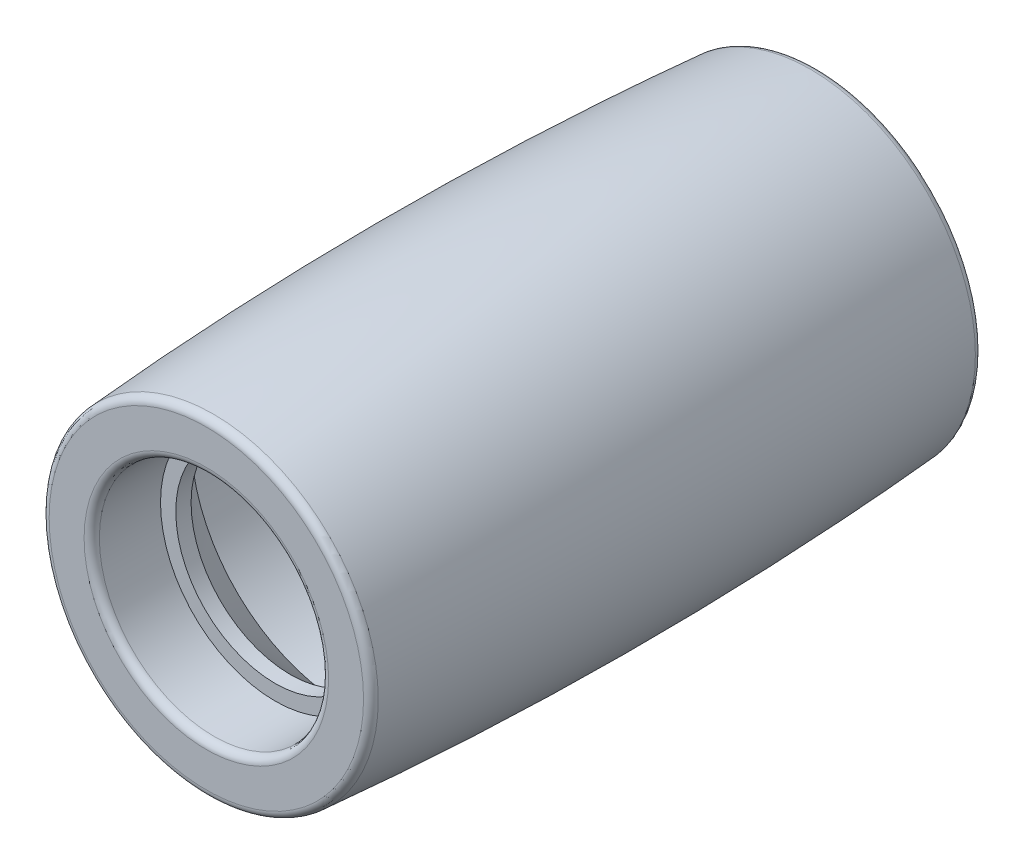
SolidWorks part; units mm, degrees
ref_plane "Ebene vorne" through (0, 0, 0) normal (0, 0, 1) x (1, 0, 0)
ref_plane "Ebene oben" through (0, 0, 0) normal (0, 1, 0) x (1, 0, 0)
ref_plane "Ebene rechts" through (0, 0, 0) normal (1, 0, 0) x (0, 0, -1)
sketch "Skizze1" plane through (450, 0, 0) normal (1, 0, 0) x (0, 0, -1)
  line L7 (20.5, 20.2121) -> (49.5, 20.2121) construction
  line L16 (49.5, 23) -> (49.5, 20.2121) construction
  line L17 (9.5, 21.5) -> (9.5, 15) construction
  line L18 (18.5, 15) -> (9.5, 15) construction
  line L19 (18.5, 15) -> (18.5, 5) construction
  line L20 (18.5, 13) -> (20.5, 13) construction
  line L21 (20.5, 13) -> (27.7121, 20.2121) construction
  line L22 (0, 0) -> (99, 0) construction
  line L23 (27.7121, 20.2121) -> (49.5, 20.2121)
  line L24 (49.5, 23) -> (49.5, 20.2121)
  line L25 (9.5, 21.5) -> (9.5, 15)
  line L26 (18.5, 15) -> (9.5, 15)
  line L27 (18.5, 15) -> (18.5, 13)
  line L28 (18.5, 13) -> (20.5, 13)
  line L29 (20.5, 13) -> (27.7121, 20.2121)
  line L30 (0, 0) -> (99, 0) construction
  arc A2 (89.5, 21.5) -> (9.5, 21.5) centre (49.5, -511.0833) ccw construction
  arc A3 (49.5, 23) -> (9.5, 21.5) centre (49.5, -511.0833) ccw
revolve "Rotation1" add sketch "Skizze1" angle 360 about L30
mirror "Spiegeln1" about plane through (450, 23, -49.5) normal (0, 0, 1) of bodies 101
fillet "Verrundung1" radius 1 4 edges at (471.5, 0, -9.5) (465, 0, -9.5) (471.5, 0, -89.5) (465, 0, -89.5)
